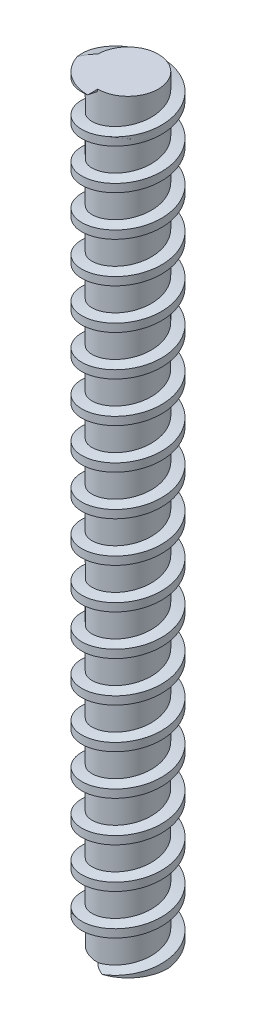
SolidWorks part; units mm, degrees
material "Stainless Steel (ferritic)"
ref_plane "Front Plane" through (0, 0, 0) normal (0, 0, 1) x (1, 0, 0)
ref_plane "Top Plane" through (0, 0, 0) normal (0, 1, 0) x (1, 0, 0)
ref_plane "Right Plane" through (0, 0, 0) normal (1, 0, 0) x (0, 0, -1)
sketch "Sketch1" plane through (0, 0, 0) normal (0, 1, 0) x (1, 0, 0)
  circle A0 centre (0, 0) radius 3
  dimension "D1" = 6
extrude "Boss-Extrude1" add sketch "Sketch1" along normal blind 85
sketch "Sketch2" plane through (0, 85, 0) normal (0, 1, 0) x (1, 0, 0)
  circle A0 centre (0, 0) radius 3
sketch "Sketch3" plane through (0, 0, 0) normal (0, 0, 1) x (1, 0, 0)
  line L0 (-3, 85) -> (-4, 84.8)
  line L1 (-4, 84.8) -> (-4, 84)
  line L2 (-4, 84) -> (-3, 83.8)
  line L3 (-3, 85) -> (-3, 0) construction
  line L4 (-3, 83.8) -> (-3, 85)
  dimension "D1" = 0.8
  dimension "D2" = 1.2
  dimension "D3" = 1
  dimension "D4" = 0.2
curve "Helix/Spiral2" pitch 4 height 84 radius 3 centre (0, 85, 0) axis (0, -1, 0) start towards (0, 0, 1)
sweep "Sweep2" add profiles "Sketch3" path "Helix/Spiral2"
sketch "Sketch5" plane through (0, 0, 0) normal (0, -1, 0) x (1, 0, 0)
  circle A0 centre (0, 0) radius 4.9187
sketch "Sketch7" plane through (0, 85, 0) normal (0, 1, 0) x (1, 0, 0)
  circle A0 centre (0, 0) radius 4.7584
extrude "Cut-Extrude6" cut sketch "Sketch7" along normal blind 7
extrude "Cut-Extrude7" cut sketch "Sketch5" against normal blind 10
sketch "Sketch9" plane through (0, 0, 0) normal (1, 0, 0) x (0, 0, -1)
  line L0 (3, 0) -> (-3, 0) construction
  line L1 (3, 0) -> (-3, 0) construction
  line L2 (0, 0) -> (0, 59.9001) construction
  line L3 (3, 85) -> (-3, 85) construction
  line L4 (3, 85) -> (-3, 85) construction
